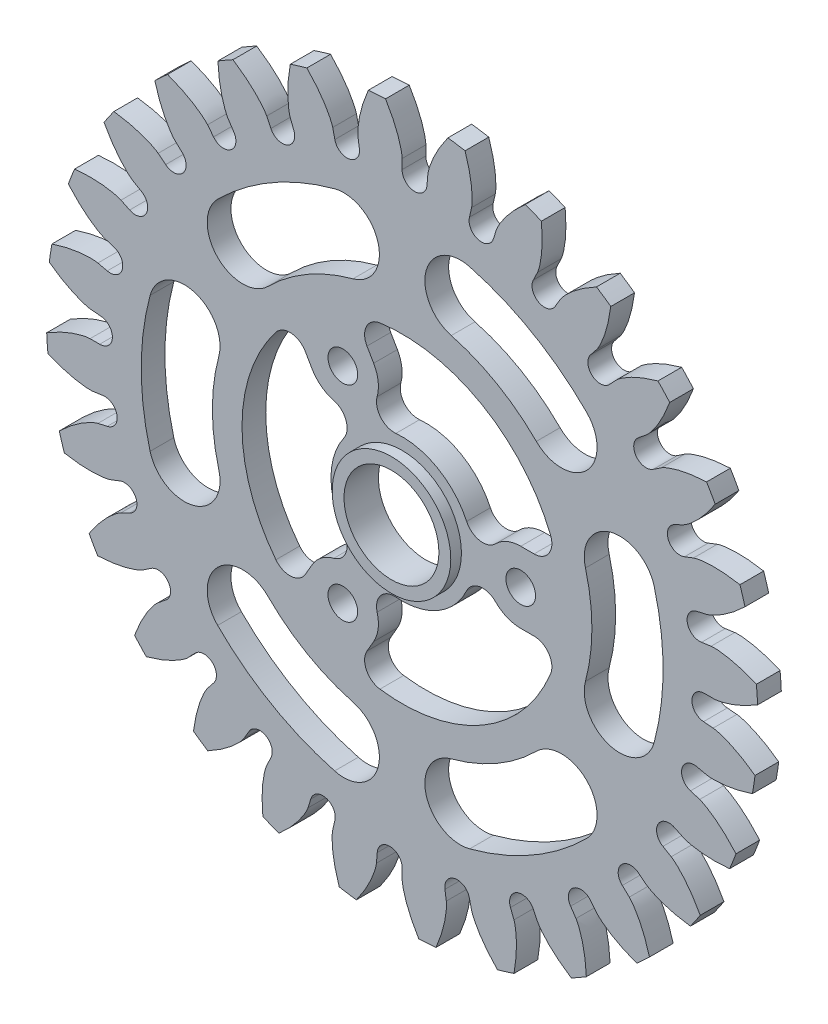
SolidWorks part; units mm, degrees
material "A2017"
ref_plane "正面" through (0, 0, 0) normal (0, 0, 1) x (1, 0, 0)
ref_plane "平面" through (0, 0, 0) normal (0, 1, 0) x (1, 0, 0)
ref_plane "右側面" through (0, 0, 0) normal (1, 0, 0) x (0, 0, -1)
sketch "ｽｹｯﾁ1" plane through (0, 0, 0) normal (1, 0, 0) x (0, 0, -1)
  line L0 (0, 0) -> (5.1985, 0) construction
  line L1 (0, 4) -> (2.9, 4)
  line L2 (2.9, 4) -> (2.9, 17.5)
  line L3 (2.9, 17.5) -> (0.9, 17.5)
  line L4 (0.9, 17.5) -> (0.9, 5)
  line L5 (0.9, 5) -> (0, 5)
  line L6 (0, 5) -> (0, 4)
  dimension "D1" = 35
  dimension "D2" = 2.9
  dimension "D3" = 2
  dimension "D4" = 10
  dimension "D5" = 8
revolve "回転1" add sketch "ｽｹｯﾁ1" angle 360 about L0
hole_wizard "M3 ねじ穴1" positions "ｽｹｯﾁ2" profile "ｽｹｯﾁ3" tap size "M3" standard "JIS" end condition through all
sketch "ｽｹｯﾁ2" plane through (0, 0, -0.9) normal (0, 0, 1) x (1, 0, 0)
  point P0 (10, 0)
  point P3 (-5, 8.6603)
  point P6 (-5, -8.6603)
sketch "ｽｹｯﾁ3" plane through (10, 0, -0.9) normal (1, 0, 0) x (0, -1, 0)
  line L0 (0, 0) -> (0, 2)
  line L1 (0, 2) -> (1.25, 2)
  line L2 (1.25, 2) -> (1.25, 0)
  line L5 (1.25, 0) -> (0, 0)
  line L11 (0, -6.35) -> (0, 107.95) construction
  dimension "次ｻｰﾌｪｽまでのねじ下穴ﾄﾞﾘﾙ直径" = 2.5
  dimension "次ｻｰﾌｪｽまでのねじ下穴ﾄﾞﾘﾙの深さ" = 2
cosmetic thread "穴のねじ山1" parameters "D2"=3
cosmetic thread "穴のねじ山2" parameters "D2"=3
cosmetic thread "穴のねじ山3" parameters "D2"=3
sketch "ｽｹｯﾁ4" plane through (0, 0, -0.9) normal (0, 0, 1) x (1, 0, 0)
  line L0 (10, 0) -> (13.5, 0) construction
  line L1 (10, 3) -> (13.5, 3)
  line L2 (10, -3) -> (13.5, -3)
  line L3 (-5, -8.6603) -> (-6.75, -11.6913) construction
  line L4 (-2.4019, -10.1603) -> (-4.1519, -13.1913)
  line L5 (-7.5981, -7.1603) -> (-9.3481, -10.1913)
  line L6 (-5, 8.6603) -> (-6.75, 11.6913) construction
  line L7 (-7.5981, 7.1603) -> (-9.3481, 10.1913)
  line L8 (-2.4019, 10.1603) -> (-4.1519, 13.1913)
  line L9 (0, 0) -> (10, 0) construction
  circle A0 centre (0, 0) radius 13.5
  arc A1 (10, 3) -> (10, -3) centre (10, 0) ccw
  arc A2 (13.5, -3) -> (13.5, 3) centre (13.5, 0) ccw
  arc A3 (-2.4019, -10.1603) -> (-7.5981, -7.1603) centre (-5, -8.6603) ccw
  arc A4 (-9.3481, -10.1913) -> (-4.1519, -13.1913) centre (-6.75, -11.6913) ccw
  arc A5 (-7.5981, 7.1603) -> (-2.4019, 10.1603) centre (-5, 8.6603) ccw
  arc A6 (-4.1519, 13.1913) -> (-9.3481, 10.1913) centre (-6.75, 11.6913) ccw
  circle A7 centre (0, 0) radius 6
  arc A8 (5.44, 2.5311) -> (7.8667, 2.1092) centre (6.8, 3.1639) ccw
  arc A9 (5.44, -2.5311) -> (7.8667, -2.1092) centre (6.8, -3.1639) cw
  arc A10 (-4.912, -3.4456) -> (-5.76, -5.7581) centre (-6.14, -4.307) cw
  arc A11 (-0.528, -5.9767) -> (-2.1067, -7.8674) centre (-0.66, -7.4709) ccw
  arc A12 (-0.528, 5.9767) -> (-2.1067, 7.8674) centre (-0.66, 7.4709) cw
  arc A13 (-4.912, 3.4456) -> (-5.76, 5.7581) centre (-6.14, 4.307) ccw
  point P6 (11.75, 0)
  point P15 (-5.875, -10.1758)
  point P22 (-5.875, 10.1758)
  point P34 (0, 0)
  point P49 (0, 0)
  dimension "D1" = 27
  dimension "D4" = 12
  dimension "D5" = 3
  dimension "D2" = 6
  dimension "D3" = 3
  dimension "D6" = 3
extrude "ｶｯﾄ - 押し出し1" cut sketch "ｽｹｯﾁ4" against normal through all contours A7 A13 A5 L7 A0 L5 A3 A10 | A12 A7 A8 A1 L1 A0 L8 A5 | A7 A11 A3 L4 A0 L2 A1 A9 region at (4.6223, 8.0061, -0.9) region at (4.6223, -8.0061, -0.9) region at (-9.2446, 0, -0.9)
fillet "ﾌｨﾚｯﾄ1" radius 1.5 6 edges at (13.1624, 3, -1.9) (-9.1793, -9.899, -1.9) (13.1624, -3, -1.9) (-3.9831, -12.899, -1.9) (-9.1793, 9.899, -1.9) (-3.9831, 12.899, -1.9)
sketch "歯車作図" plane through (0, 0, -0.9) normal (0, 0, 1) x (1, 0, 0)
  line L0 (0, 0) -> (25.5, 0) construction
  line L1 (25.5, 0) -> (26.3114, 0)
  line L2 (0, 0) -> (29.9745, -1.2355)
  circle A0 centre (0, 0) radius 30
  circle A1 centre (0, 0) radius 28 construction
  circle A2 centre (0, 0) radius 26.3114 construction
  circle A3 centre (0, 0) radius 25.5 construction
  arc A4 (27.9762, -1.1531) -> (27.9969, 0.4173) centre (0, 0) ccw
  spline S0 degree 4 poles (26.3114, 0) (26.3519, 0.0013) (26.4329, 0.0063) (26.6589, 0.033) (27.0848, 0.1166) (27.7247, 0.3006) (28.5755, 0.6367) (29.6254, 1.1673) (30.7905, 1.9033) (31.9912, 2.8259) (33.1927, 3.9303) (34.3032, 5.1257) (35.3247, 6.3978) (36.3053, 7.8011) (37.4014, 9.6156) (38.528, 11.8801) (39.5864, 14.6214) (40.4562, 17.7686) (41.0337, 20.9817) (41.3324, 24.232) (41.3656, 27.4956) (41.1738, 30.3444) (40.8594, 32.7708) (40.5015, 34.7769) (40.1586, 36.3716) (39.762, 37.9517) (39.3106, 39.5208) (38.8102, 41.0681) (38.3238, 42.4169) (37.8838, 43.5452) (37.5131, 44.4365) (37.2634, 45.0171) (36.9734, 45.666) (36.7803, 46.0867) (36.463, 46.7613) (36.2065, 47.2825) (35.8912, 47.9127) (35.6004, 48.4699) (35.2823, 49.0677) (34.9714, 49.6307) (34.7238, 50.0704) (34.5624, 50.3492) (34.4786, 50.4938) knots 0 0 0 0 0 0.002802 0.005604 0.015718 0.02996 0.048734 0.068727 0.096889 0.125051 0.153212 0.181374 0.209535 0.237696 0.271429 0.327752 0.384075 0.440398 0.496721 0.553044 0.609367 0.66569 0.693852 0.722013 0.750174 0.778336 0.806497 0.834659 0.86282 0.876901 0.890982 0.900036 0.909091 0.920455 0.931818 0.943182 0.954545 0.965909 0.977273 0.988636 1 1 1 1 1 construction
  spline S1 degree 4 poles (26.3114, 0) (26.3519, 0.0013) (26.4329, 0.0063) (26.6589, 0.033) (27.0848, 0.1166) (27.7247, 0.3006) (28.5755, 0.6367) (29.6254, 1.1673) (30.7905, 1.9033) (31.9912, 2.8259) (33.1927, 3.9303) (34.3032, 5.1257) (35.3247, 6.3978) (36.3053, 7.8011) (37.4014, 9.6156) (38.528, 11.8801) (39.5864, 14.6214) (40.4562, 17.7686) (41.0337, 20.9817) (41.3324, 24.232) (41.3656, 27.4956) (41.1738, 30.3444) (40.8594, 32.7708) (40.5015, 34.7769) (40.1586, 36.3716) (39.762, 37.9517) (39.3106, 39.5208) (38.8102, 41.0681) (38.3238, 42.4169) (37.8838, 43.5452) (37.5131, 44.4365) (37.2634, 45.0171) (37.049, 45.4967) (36.9499, 45.7154) (36.9004, 45.8237) knots 0 0 0 0 0 0.002802 0.005604 0.015718 0.02996 0.048734 0.068727 0.096889 0.125051 0.153212 0.181374 0.209535 0.237696 0.271429 0.327752 0.384075 0.440398 0.496721 0.553044 0.609367 0.66569 0.693852 0.722013 0.750174 0.778336 0.806497 0.834659 0.86282 0.876901 0.890982 0.900036 0.909091 0.909091 0.909091 0.909091 0.909091
  dimension "歯先円直径" = 60
  dimension "基礎ピッチ円直径" = 56
  dimension "基礎円直径" = 52.6228
  dimension "全歯丈" = 4.5
  dimension "基準ピッチ" = 1.5708
sketch "ｽｹｯﾁ6" plane through (0, 0, -0.9) normal (0, 0, 1) x (1, 0, 0)
  circle A0 centre (0, 0) radius 30 construction
  circle A1 centre (0, 0) radius 30
  circle A3 centre (0, 0) radius 17.5
  circle A4 centre (0, 0) radius 17.5
  dimension "D1" = 0
extrude "ﾎﾞｽ - 押し出し1" add sketch "ｽｹｯﾁ6" against normal through all
sketch "ｽｹｯﾁ7" plane through (0, 0, -0.9) normal (0, 0, 1) x (1, 0, 0)
  line L0 (25.5, 0) -> (26.3114, 0) construction
  line L1 (0, 0) -> (29.9745, -1.2355) construction
  line L2 (25.5, 0) -> (26.3114, 0)
  line L3 (25.4784, -1.0502) -> (29.9745, -1.2355)
  circle A1 centre (0, 0) radius 30
  arc A2 (29.9745, -1.2355) -> (29.9674, 1.3986) centre (0, 0) ccw
  circle A3 centre (0, 0) radius 25.5 construction
  arc A4 (25.4784, -1.0502) -> (25.5, 0) centre (0, 0) ccw
  spline S0 degree 4 poles (18.0064, -999.7701) (20.0439, 38.1516) (22.4374, 0.7712) (24.776, -0.3364) (27.0848, 0.1166) (27.7247, 0.3006) (28.5755, 0.6367) (29.6254, 1.1673) (30.7905, 1.9033) (31.9912, 2.8259) (33.1927, 3.9303) (34.3032, 5.1257) (35.3247, 6.3978) (36.3053, 7.8011) (37.4014, 9.6156) (38.528, 11.8801) (39.5864, 14.6214) (40.4562, 17.7686) (41.0337, 20.9817) (41.3324, 24.232) (41.3656, 27.4956) (41.1738, 30.3444) (40.8594, 32.7708) (40.5015, 34.7769) (40.1586, 36.3716) (39.762, 37.9517) (39.3106, 39.5208) (38.8102, 41.0681) (38.3238, 42.4169) (37.8838, 43.5452) (37.5131, 44.4365) (36.5867, 46.5912) (34.7604, 50.3825) (49.4042, 17.9493) (-379.6911, 954.9172) knots -0.132452 -0.132452 -0.132452 -0.132452 -0.132452 0.002802 0.005604 0.015718 0.02996 0.048734 0.068727 0.096889 0.125051 0.153212 0.181374 0.209535 0.237696 0.271429 0.327752 0.384075 0.440398 0.496721 0.553044 0.609367 0.66569 0.693852 0.722013 0.750174 0.778336 0.806497 0.834659 0.86282 0.876901 0.890982 0.900036 1.034522 1.034522 1.034522 1.034522 1.034522 only from (26.3114, 0) to (36.9004, 45.8237) construction
  spline S1 degree 4 poles (26.3114, 0) (26.3519, 0.0013) (26.4329, 0.0063) (26.6589, 0.033) (27.0848, 0.1166) (27.7247, 0.3006) (28.5683, 0.6339) (29.2472, 0.9762) (29.727, 1.252) (29.9674, 1.3986) knots 0 0 0 0 0 0.002802 0.005604 0.015718 0.02996 0.048734 0.06819 0.06819 0.06819 0.06819 0.06819
  dimension "D1" = 0
extrude "ｶｯﾄ - 押し出し2" cut sketch "ｽｹｯﾁ7" against normal through all
pattern_circular "円形ﾊﾟﾀｰﾝ1" count 28 over 360 about axis through (0, 0, 0) along (0, 0, 1) of "ｶｯﾄ - 押し出し2"
mirror "ﾐﾗｰ1" about plane through (25.4784, -1.0502, -2.9) normal (-0.0412, -0.9992, 0) of "円形ﾊﾟﾀｰﾝ1"
sketch "ｽｹｯﾁ8" plane through (0, 0, -0.9) normal (0, 0, 1) x (1, 0, 0)
  circle A0 centre (1.0502, 25.4784) radius 1.0504
  arc A1 (2.0986, 25.4135) -> (0, 25.5) centre (0, 0) ccw construction
extrude "ｶｯﾄ - 押し出し3" cut sketch "ｽｹｯﾁ8" against normal through all
pattern_circular "円形ﾊﾟﾀｰﾝ2" count 28 over 360 about axis through (0, 0, 0) along (0, 0, 1) of "ｶｯﾄ - 押し出し3"
sketch "ｽｹｯﾁ9" plane through (0, 0, -0.9) normal (0, 0, 1) x (1, 0, 0)
  line L0 (0, 0) -> (19, 0) construction
  line L1 (0, 0) -> (18.3526, -4.9176) construction
  line L2 (18.3526, 4.9176) -> (0, 0) construction
  circle A0 centre (0, 0) radius 16 construction
  circle A1 centre (0, 0) radius 22 construction
  arc A2 (18.3526, -4.9176) -> (18.3526, 4.9176) centre (0, 0) ccw construction
  arc A3 (21.2504, -5.694) -> (21.2504, 5.694) centre (0, 0) ccw
  arc A4 (15.4548, -4.1411) -> (15.4548, 4.1411) centre (0, 0) ccw
  arc A5 (15.4548, -4.1411) -> (21.2504, -5.694) centre (18.3526, -4.9176) ccw
  arc A6 (21.2504, 5.694) -> (15.4548, 4.1411) centre (18.3526, 4.9176) ccw
  arc A7 (4.9176, -18.3526) -> (13.435, -13.435) centre (0, 0) ccw construction
  arc A8 (5.694, -21.2504) -> (15.5563, -15.5563) centre (0, 0) ccw
  arc A9 (4.1411, -15.4548) -> (11.3137, -11.3137) centre (0, 0) ccw
  arc A10 (4.1411, -15.4548) -> (5.694, -21.2504) centre (4.9176, -18.3526) ccw
  arc A11 (15.5563, -15.5563) -> (11.3137, -11.3137) centre (13.435, -13.435) ccw
  arc A12 (-13.435, -13.435) -> (-4.9176, -18.3526) centre (0, 0) ccw construction
  arc A13 (-15.5563, -15.5563) -> (-5.694, -21.2504) centre (0, 0) ccw
  arc A14 (-11.3137, -11.3137) -> (-4.1411, -15.4548) centre (0, 0) ccw
  arc A15 (-11.3137, -11.3137) -> (-15.5563, -15.5563) centre (-13.435, -13.435) ccw
  arc A16 (-5.694, -21.2504) -> (-4.1411, -15.4548) centre (-4.9176, -18.3526) ccw
  arc A17 (-18.3526, 4.9176) -> (-18.3526, -4.9176) centre (0, 0) ccw construction
  arc A18 (-21.2504, 5.694) -> (-21.2504, -5.694) centre (0, 0) ccw
  arc A19 (-15.4548, 4.1411) -> (-15.4548, -4.1411) centre (0, 0) ccw
  arc A20 (-15.4548, 4.1411) -> (-21.2504, 5.694) centre (-18.3526, 4.9176) ccw
  arc A21 (-21.2504, -5.694) -> (-15.4548, -4.1411) centre (-18.3526, -4.9176) ccw
  arc A22 (-4.9176, 18.3526) -> (-13.435, 13.435) centre (0, 0) ccw construction
  arc A23 (-5.694, 21.2504) -> (-15.5563, 15.5563) centre (0, 0) ccw
  arc A24 (-4.1411, 15.4548) -> (-11.3137, 11.3137) centre (0, 0) ccw
  arc A25 (-4.1411, 15.4548) -> (-5.694, 21.2504) centre (-4.9176, 18.3526) ccw
  arc A26 (-15.5563, 15.5563) -> (-11.3137, 11.3137) centre (-13.435, 13.435) ccw
  arc A27 (13.435, 13.435) -> (4.9176, 18.3526) centre (0, 0) ccw construction
  arc A28 (15.5563, 15.5563) -> (5.694, 21.2504) centre (0, 0) ccw
  arc A29 (11.3137, 11.3137) -> (4.1411, 15.4548) centre (0, 0) ccw
  arc A30 (11.3137, 11.3137) -> (15.5563, 15.5563) centre (13.435, 13.435) ccw
  arc A31 (5.694, 21.2504) -> (4.1411, 15.4548) centre (4.9176, 18.3526) ccw
  point P6 (19, 0)
  point P20 (9.5, -16.4545)
  point P27 (-9.5, -16.4545)
  point P34 (-19, 0)
  point P41 (-9.5, 16.4545)
  point P48 (9.5, 16.4545)
  point P53 (0, 0)
  dimension "D1" = 32
  dimension "D2" = 44
  dimension "D3" = 6
  dimension "D4" = 30
  dimension "D5" = 6
extrude "ｶｯﾄ - 押し出し4" cut sketch "ｽｹｯﾁ9" against normal through all
equation "\"モジュール\"= 2"
equation "\"歯数\"= 28"
equation "\"圧力角\"= 20"
equation "\"歯先円直径@歯車作図\" =  ( \"歯数\" + 2 )  * \"モジュール\""
equation "\"基礎ピッチ円直径@歯車作図\" = \"モジュール\" * \"歯数\""
equation "\"基礎円直径@歯車作図\" = \"歯数\" * \"モジュール\" * cos ( \"圧力角\" ) "
equation "\"全歯丈@歯車作図\" = 2.25 * \"モジュール\""
equation "\"基準ピッチ@歯車作図\" = PI * \"モジュール\" / 4"
equation "\"D1@円形ﾊﾟﾀｰﾝ1\"=\"歯数\""
equation "\"D1@円形ﾊﾟﾀｰﾝ2\"=\"歯数\""
